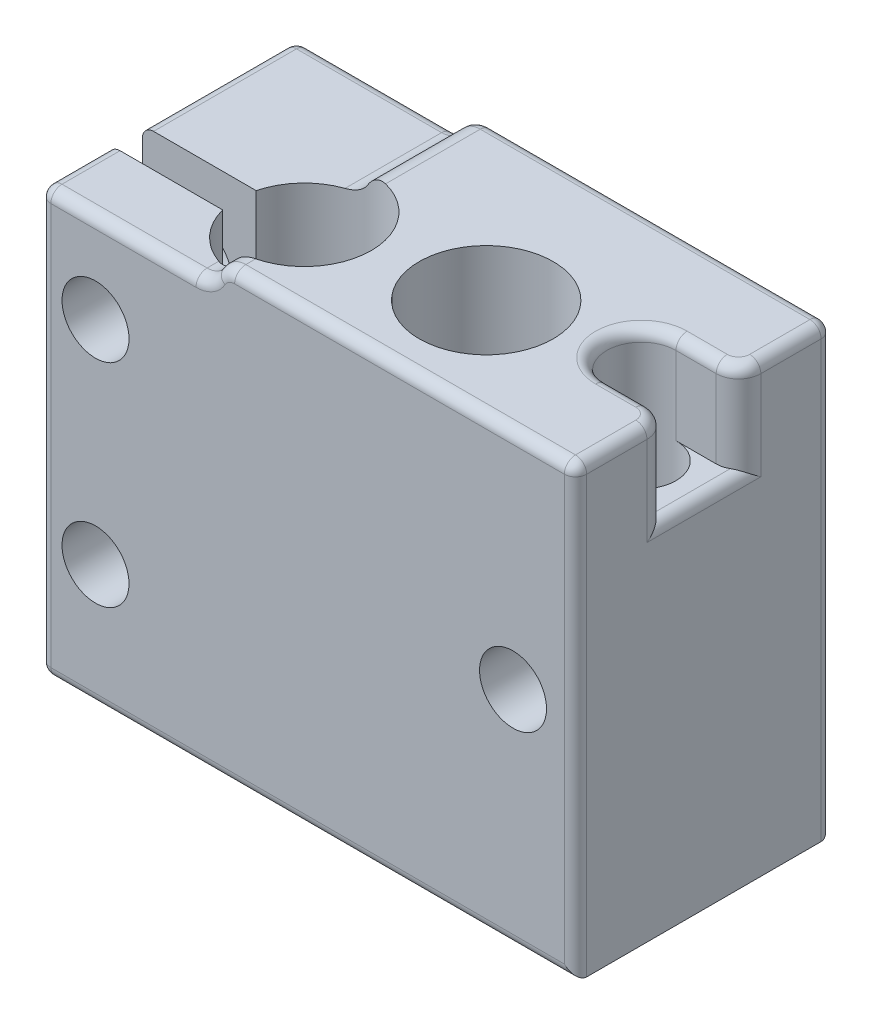
SolidWorks part; units mm, degrees
ref_plane "Płaszczyzna przednia" through (0, 0, 0) normal (0, 0, 1) x (1, 0, 0)
ref_plane "Płaszczyzna górna" through (0, 0, 0) normal (0, 1, 0) x (1, 0, 0)
ref_plane "Płaszczyzna prawa" through (0, 0, 0) normal (1, 0, 0) x (0, 0, -1)
sketch "Szkic1" plane through (0, 0, 0) normal (0, 1, 0) x (1, 0, 0)
  line L0 (12, 0) -> (-12, 0) construction
  line L1 (12, -5.75) -> (-12, -5.75)
  line L2 (12, -5.75) -> (12, 5.75)
  line L3 (12, 5.75) -> (-12, 5.75)
  line L4 (-12, -5.75) -> (-12, -2.65)
  line L5 (9.2, 1.55) -> (12, 1.55)
  line L6 (9.2, -1.55) -> (12, -1.55)
  line L7 (-12, -1.15) -> (-12, 5.75)
  line L8 (-12, -2.65) -> (-6.9047, -2.65)
  line L9 (-12, -1.15) -> (-6.9047, -1.15)
  circle A0 centre (9.2, 0) radius 1.55
  circle A1 centre (3.5, -1.25) radius 3
  arc A2 (-6.9047, -2.65) -> (-6.9047, -1.15) centre (-4, -1.9) ccw
  point P0 (0, 0)
  point P18 (-14.9217, -1.9)
  point P19 (-5.6013, -1.9)
  point P20 (-14.9217, -2.65)
  point P21 (-5.6013, -2.65)
  point P22 (-14.9217, -1.15)
  point P23 (-5.6013, -1.15)
  dimension "D3" = 3.1
  dimension "D5" = 6
  dimension "D8" = 6
  dimension "D1" = 11.5
  dimension "D2" = 24
  dimension "D4" = 21.2
  dimension "D6" = 4.5
  dimension "D7" = 15.5
  dimension "D9" = 3.85
  dimension "D10" = 8
extrude "Dodanie-wyciągnięcie1" add sketch "Szkic1" against normal blind 20 contours L0 A0 L5 L2 L3 L7 A2 A1 | A2 L0 L7 L9 | A0 L0 A1 A2 L8 L4 L1 L2 L6 | L2 L0 A0 L6 | L0 L2 L5 A0 region at (11.1709, 0, 0.8651) region at (11.1709, 0, -0.8651) region at (1.2595, 0, 3.8737) region at (-0.5926, 0, -3.1774) region at (-9.3302, 0, 0.5646)
extrude "Wytnij-wyciągnięcie1" cut sketch "Szkic1<4>" against normal blind 4 contours L0 L2 L5 A0 | L2 L0 A0 L6 region at (11.1709, 0, 0.8651) region at (11.1709, 0, -0.8651)
sketch "Szkic1<4>" plane through (0, 0, 0) normal (0, 1, 0) x (1, 0, 0) same geometry as "Szkic1"
sketch "Szkic2" plane through (0, 0, 5.75) normal (0, 0, 1) x (1, 0, 0)
  line L0 (-9.5, -20) -> (-9.5, 0) construction
  line L1 (12, -20) -> (-12, -20) construction
  line L2 (12, 0) -> (-12, 0) construction
  line L3 (-12, -20) -> (-12, 0) construction
  line L4 (-12, -1) -> (-4, -1)
  line L6 (-4, 0) -> (-4, -1)
  line L7 (-4, 0) -> (-12, 0)
  line L8 (-12, 0) -> (-12, -1)
  circle A0 centre (-9.5, -5) radius 1.5
  circle A1 centre (-9.5, -14.5) radius 1.5
  circle A2 centre (9.2, -10) radius 1.5
  point P15 (-4, -0.5)
  dimension "D2" = 3
  dimension "D3" = 3
  dimension "D4" = 3
  dimension "D1" = 2.5
  dimension "D5" = 15
  dimension "D6" = 5.5
  dimension "D7" = 19
  dimension "D8" = 90
  dimension "D9" = 8
  dimension "D10" = 10
  dimension "D11" = 21.2
extrude "Wytnij-wyciągnięcie2" cut sketch "Szkic2" against normal through all contours L7 L8 L4 L6
extrude "Wytnij-wyciągnięcie3" cut sketch "Szkic2<3>" against normal blind 5.5 contours A2 region at (9.2, -10, 5.75)
sketch "Szkic2<3>" plane through (0, 0, 5.75) normal (0, 0, 1) x (1, 0, 0) same geometry as "Szkic2"
extrude "Wytnij-wyciągnięcie4" cut sketch "Szkic2<4>" against normal through all contours A0 | A1
sketch "Szkic2<4>" plane through (0, 0, 5.75) normal (0, 0, 1) x (1, 0, 0) same geometry as "Szkic2"
fillet "Zaokrąglenie1" radius 1 2 edges at (-4, -1, -3.425) (-4, -1, 5.325)
fillet "Zaokrąglenie2" radius 1 2 edges at (-4, 0, 5.325) (-4, 0, -3.425)
fillet "Zaokrąglenie3" radius 1 2 edges at (12, -2, 1.55) (12, -2, -1.55)
fillet "Zaokrąglenie4" radius 0.5 25 edges at (12, 0, 4.15) (11.7071, 0, 1.8429) (10.1, 0, 1.55) (7.65, 0, 0) (10.1, 0, -1.55) (11.7071, 0, -1.8429) (4.366, 0, -5.75) (-3.7679, -0.134, -5.75) (-4.5, -0.866, -5.75) (-8.5, -1, 5.75) (-4.5, -0.866, 5.75) (-3.7679, -0.134, 5.75) (-12, -10.5, -5.75) (-12, -20, 4.2) (-12, -20, -2.3) (0, -20, -5.75) (0, -20, 5.75) (-12, -10.5, 5.75) (12, 0, -4.15) (-8.5, -1, -5.75) (-12, -1, -2.3) (-12, -1, 4.2) (4.366, 0, 5.75) (12, -10, -5.75) (12, -10, 5.75)
fillet "Zaokrąglenie5" radius 0.5 1 edges at (12, -4, 0)
